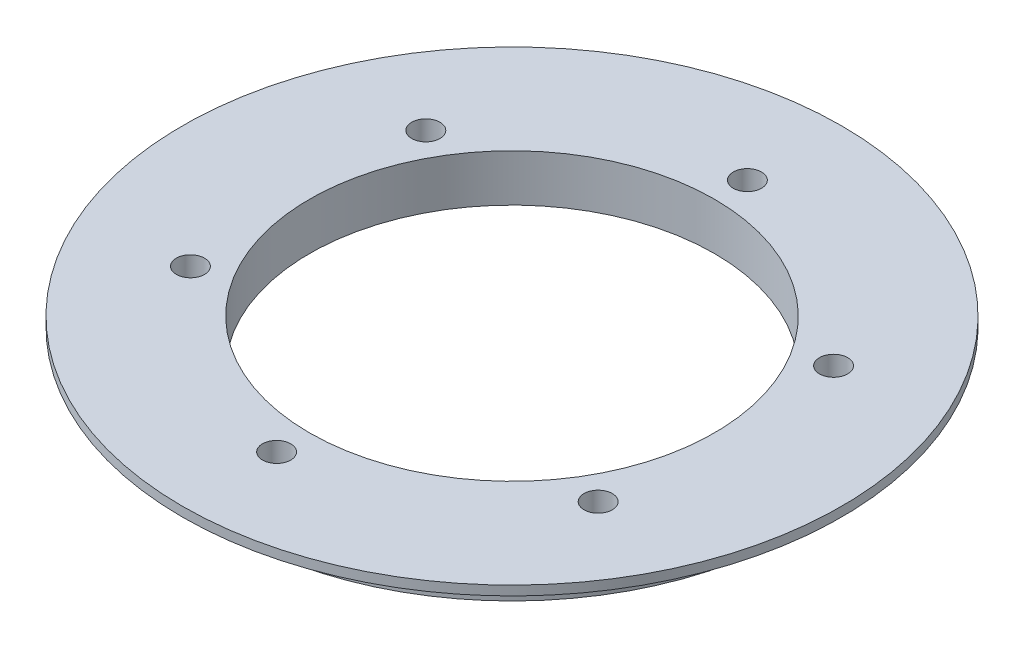
SolidWorks part; units mm, degrees
ref_plane "Front Plane" through (0, 0, 0) normal (0, 0, 1) x (1, 0, 0)
ref_plane "Top Plane" through (0, 0, 0) normal (0, 1, 0) x (1, 0, 0)
ref_plane "Right Plane" through (0, 0, 0) normal (1, 0, 0) x (0, 0, -1)
sketch "Sketch1" plane through (0, 0, 0) normal (0, 1, 0) x (1, 0, 0)
  circle A0 centre (0, 0) radius 30
  circle A2 centre (0, 0) radius 25 construction
  dimension "D1" = 60
  dimension "D2" = 50
extrude "Boss-Extrude1" add sketch "Sketch1" along normal blind 5
sketch "Sketch2" plane through (0, 5, 0) normal (0, 1, 0) x (1, 0, 0)
  circle A0 centre (0, 0) radius 35
  dimension "D1" = 70
extrude "Boss-Extrude2" add sketch "Sketch2" against normal blind 1
sketch "Sketch3" plane through (0, 0, 0) normal (0, -1, 0) x (1, 0, 0)
  circle A0 centre (0, 0) radius 21.5
  dimension "D1" = 43
extrude "Cut-Extrude1" cut sketch "Sketch3" against normal blind 25
sketch "Sketch4" plane through (0, 5, 0) normal (0, 1, 0) x (1, 0, 0)
  circle A0 centre (0, 0) radius 25 construction
  circle A1 centre (0, 25) radius 1.5
  circle A2 centre (0, 0) radius 25 construction
  circle A3 centre (21.6506, 12.5) radius 1.5
  circle A4 centre (0, 0) radius 25 construction
  circle A5 centre (21.6506, -12.5) radius 1.5
  circle A6 centre (0, 0) radius 25 construction
  circle A7 centre (0, -25) radius 1.5
  circle A8 centre (0, 0) radius 25 construction
  circle A9 centre (-21.6506, -12.5) radius 1.5
  circle A10 centre (0, 0) radius 25 construction
  circle A11 centre (-21.6506, 12.5) radius 1.5
  point P22 (0, 0)
  dimension "D1" = 50
  dimension "D2" = 3
  dimension "D3" = 6
extrude "Cut-Extrude2" cut sketch "Sketch4" against normal blind 25
